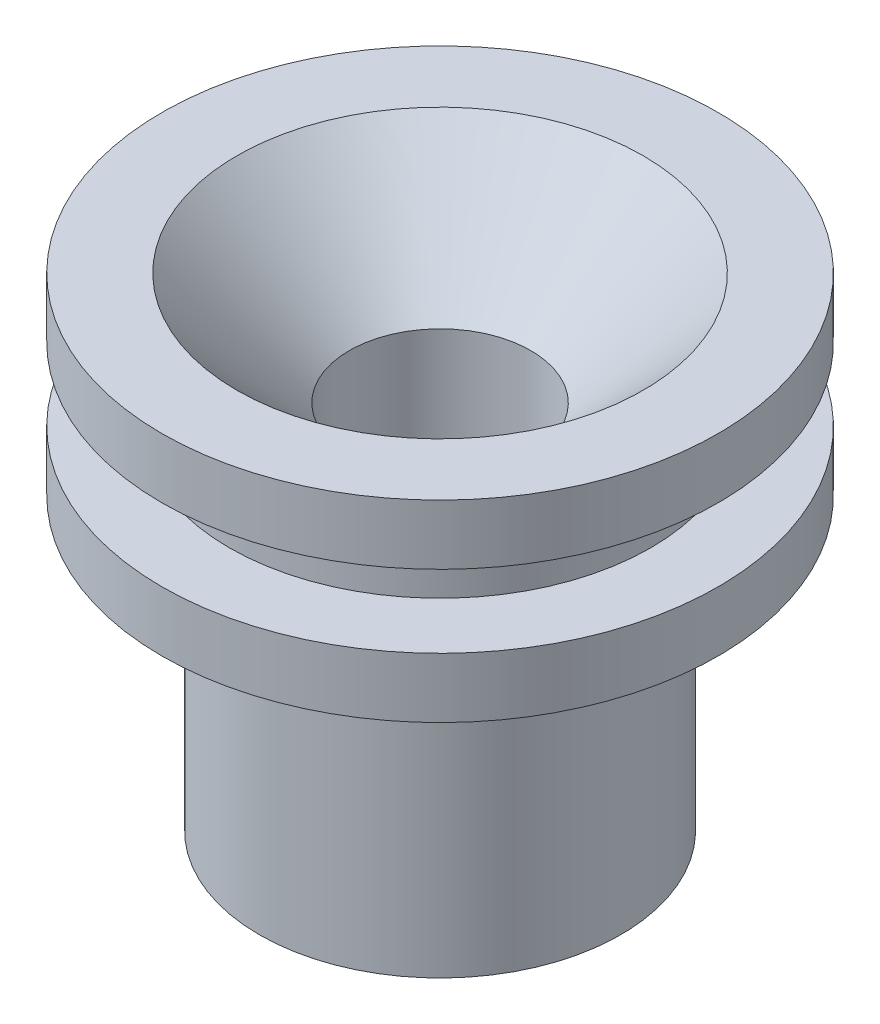
SolidWorks part; units mm, degrees
ref_plane "Front Plane" through (0, 0, 0) normal (0, 0, 1) x (1, 0, 0)
ref_plane "Top Plane" through (0, 0, 0) normal (0, 1, 0) x (1, 0, 0)
ref_plane "Right Plane" through (0, 0, 0) normal (1, 0, 0) x (0, 0, -1)
sketch "Sketch1" plane through (0, 0, 0) normal (0, 0, 1) x (1, 0, 0)
  line L0 (0, 0) -> (6.1214, 0)
  line L1 (6.1214, 0) -> (6.1214, 9.8298)
  line L2 (0, 0) -> (0, 9.8298)
  line L4 (9.4234, 9.8298) -> (9.4234, 11.8618)
  line L5 (9.4234, 11.8618) -> (7.1374, 11.8618)
  line L6 (7.1374, 11.8618) -> (7.1374, 14.3256)
  line L7 (7.1374, 14.3256) -> (9.4234, 14.3256)
  line L8 (9.4234, 14.3256) -> (9.4234, 16.3576)
  line L9 (9.4234, 16.3576) -> (0, 16.3576)
  line L10 (0, 16.3576) -> (0, 9.8298)
  line L11 (9.4234, 9.8298) -> (6.1214, 9.8298)
revolve "Revolve1" add sketch "Sketch1" angle 360 about L10
sketch "Sketch2" plane through (0, 16.3576, 0) normal (0, 1, 0) x (1, 0, 0)
  circle A0 centre (0, 0) radius 3.0734
extrude "Cut-Extrude1" cut sketch "Sketch2" against normal blind 15.494
sketch "Sketch3" plane through (0, 0, 0) normal (0, -1, 0) x (1, 0, 0)
  circle A0 centre (0, 0) radius 1.5494
extrude "Cut-Extrude2" cut sketch "Sketch3" against normal through all
chamfer "Chamfer1" distance 3.81 angle 45 1 edges at (0, 16.3576, 3.0734)
ref_axis "Axis1" through (0, 17.1755, 0) along (0, -1, 0)
